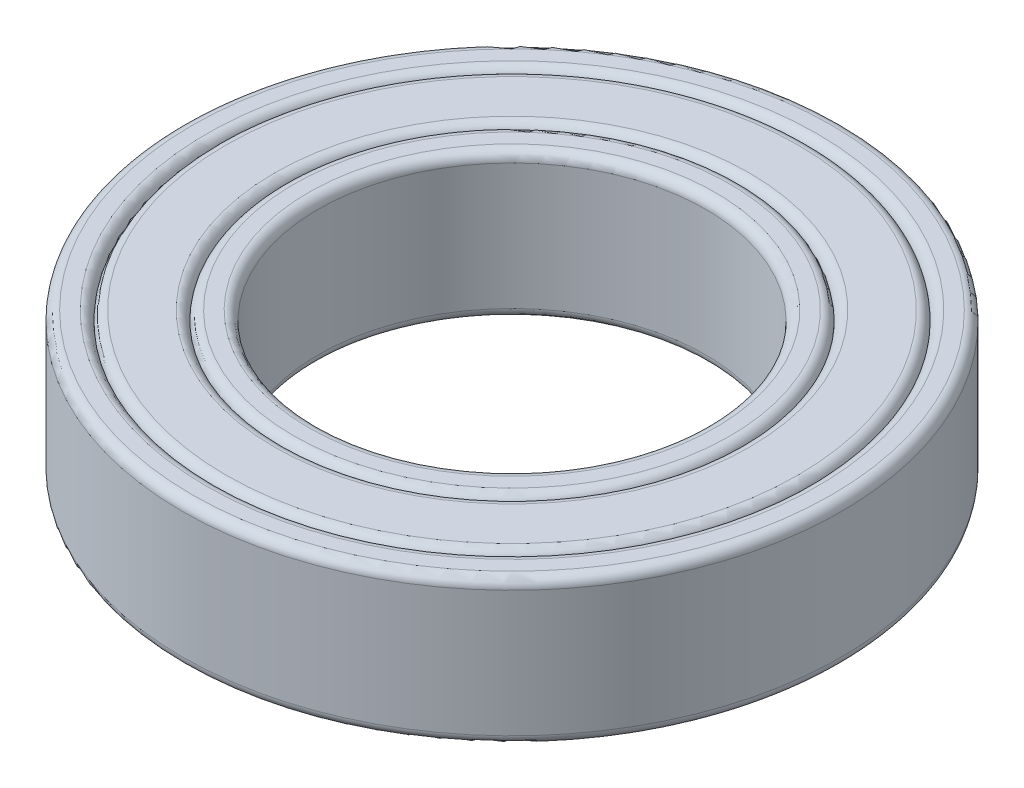
SolidWorks part; units mm, degrees
ref_plane "Front Plane" through (0, 0, 0) normal (0, 0, 1) x (1, 0, 0)
ref_plane "Top Plane" through (0, 0, 0) normal (0, 1, 0) x (1, 0, 0)
ref_plane "Right Plane" through (0, 0, 0) normal (1, 0, 0) x (0, 0, -1)
sketch "Sketch1" plane through (0, 0, 0) normal (0, 1, 0) x (1, 0, 0)
  circle A0 centre (0, 0) radius 34
  dimension "D1" = 68
extrude "Boss-Extrude1" add sketch "Sketch1" along normal mid plane 15
fillet "Fillet1" radius 1 2 edges at (0, -7.5, 34) (0, 7.5, 34)
sketch "Sketch2" plane through (0, 0, 0) normal (0, 1, 0) x (1, 0, 0)
  circle A0 centre (0, 0) radius 30.5
  dimension "D1" = 61
extrude "Cut-Extrude1" cut sketch "Sketch2" against normal through all both and the other way through all
fillet "Fillet2" radius 1 2 edges at (0, 7.5, 30.5) (0, -7.5, 30.5)
sketch "Sketch3" plane through (0, 0, 0) normal (0, 1, 0) x (1, 0, 0)
  circle A0 centre (0, 0) radius 30.5
  dimension "D1" = 61
extrude "Boss-Extrude2" add sketch "Sketch3" along normal through all and the other way through all
fillet "Fillet3" radius 1 2 edges at (0, -7.5, 30.5) (0, 7.5, 30.5)
sketch "Sketch4" plane through (0, 0, 0) normal (0, 1, 0) x (1, 0, 0)
  circle A0 centre (0, 0) radius 23.5
  dimension "D1" = 47
extrude "Cut-Extrude2" cut sketch "Sketch4" against normal through all both and the other way through all
fillet "Fillet4" radius 1 2 edges at (0, 7.5, 23.5) (0, -7.5, 23.5)
sketch "Sketch5" plane through (0, 0, 0) normal (0, 1, 0) x (1, 0, 0)
  circle A0 centre (0, 0) radius 23.5
  dimension "D1" = 47
extrude "Boss-Extrude3" add sketch "Sketch5" along normal through all and the other way through all
fillet "Fillet5" radius 1 2 edges at (0, -7.5, 23.5) (0, 7.5, 23.5)
sketch "Sketch6" plane through (0, 0, 0) normal (0, 1, 0) x (1, 0, 0)
  circle A0 centre (0, 0) radius 20
  dimension "D1" = 40
extrude "Cut-Extrude3" cut sketch "Sketch6" against normal through all both and the other way through all
fillet "Fillet6" radius 1 2 edges at (0, 7.5, 20) (0, -7.5, 20)
equation "\"D1@Boss-Extrude1\" = \"ARM Rotating Bearing Thickness\""
equation "\"D1@Sketch1\" = \"ARM Rotating Bearing OD\""
equation "\"D1@Fillet1\" = \"ALL Medium Fillet\""
equation "\"D1@Fillet2\" = \"ALL Medium Fillet\""
equation "\"D1@Fillet3\" = \"ALL Medium Fillet\""
equation "\"D1@Fillet4\" = \"ALL Medium Fillet\""
equation "\"D1@Fillet5\" = \"ALL Medium Fillet\""
equation "\"D1@Fillet6\"= \"ALL Medium Fillet\""
equation "\"D1@Sketch2\" = \"ARM Rotating Bearing OD\" - ( ( \"ARM Rotating Bearing OD\" - \"ARM Rotating Bearing ID\" ) / 4 )"
equation "\"D1@Sketch6\" = \"ARM Rotating Bearing ID\""
equation "\"D1@Sketch4\" = \"ARM Rotating Bearing ID\" + ( ( \"ARM Rotating Bearing OD\" - \"ARM Rotating Bearing ID\" ) / 4 )"
equation "\"D1@Sketch3\" = \"ARM Rotating Bearing OD\" - ( ( \"ARM Rotating Bearing OD\" - \"ARM Rotating Bearing ID\" ) / 4 )"
equation "\"D1@Sketch5\" = \"ARM Rotating Bearing ID\" + ( ( \"ARM Rotating Bearing OD\" - \"ARM Rotating Bearing ID\" ) / 4 )"
equation "\"ALL Big Fillet\"= 10.0mm"
equation "\"ALL Medium Fillet\"= 1.0mm"
equation "\"ALL Small Fillet\"= 0.5mm"
equation "\"BODY Rad\"= 82.5mm"
equation "\"BODY End Cut Rad\"= 72.5mm"
equation "\"BODY Height Ext\"= 27.5mm"
equation "\"BODY Bottom Cut Dist\"= 50.0mm"
equation "\"BODY Seal Thickness\"= 3.75mm"
equation "\"BODY Wall Extra Thickness\"= 2.5mm"
equation "\"BODY Bottom Extra Nut Wall\"= 7.5mm"
equation "\"ARM Both Dia\"= 39.75mm"
equation "\"ARM Both Length\"= 67.5mm"
equation "\"ARM Both Wire Hole Dia\"= 15.0mm"
equation "\"ARM Both Prop Seal Thickness\"= 2.5mm"
equation "\"ARM Both Brass Insert Dia\"= 4.875mm"
equation "\"ARM Both Bolt Cut Depth\"= 12.5mm"
equation "\"ARM Both Nema Bolt Off\"= 15.4mm"
equation "\"ARM Both Nema Bolt Depth\"= 2.5mm"
equation "\"ARM Both Nema Width\"= 20.0mm"
equation "\"ARM Both Nema Wall Off\"= 2.5mm"
equation "\"ARM Both Nema Center Dia 1\"= 17.0mm"
equation "\"ARM Both Nema Center Dia 2\"= 10.0mm"
equation "\"ARM Both Nema Bearing OD\"= 16.0mm"
equation "\"ARM Both Nema Bearing ID\"= 10.0mm"
equation "\"ARM Both Nema Bearing Thickness\"= 4.0mm"
equation "\"ARM Both Nema Height\"= 38.0mm"
equation "\"ARM Both Nema Shaft Dia\"= 4.0mm"
equation "\"ARM Both Nema Shaft Length\"= 10.0mm"
equation "\"ARM Both Nema Center Height\"= 1.5mm"
equation "\"ARM Rotating Bearing OD\"= 68.0mm"
equation "\"ARM Rotating Bearing ID\"= 40.0mm"
equation "\"ARM Rotating Bearing Thickness\"= 15.0mm"
equation "\"ARM Static Mount Dia\"= 65.0mm"
equation "\"ARM Static Bolt Off\"= 1.125mm"
equation "\"ALL Bolt Hole Off\"= 0.25mm"
equation "\"ALL Vert Bolt Hole Off Scalar\"= 0.5mm"
equation "\"ALL Horz Bolt Hole Off Scalar\"= 1.25mm"
equation "\"ALL Nut Size Off\"= 0.25mm"
equation "\"ALL Vert Nut Off Scalar\"= 0.5mm"
equation "\"ALL Horz Nut Off Scalar\"= 1.25mm"
equation "\"BODY Bolt Count\"= 12"
equation "\"BODY Bolt Size\"= 6"
equation "\"BODY Bolt Length\"= 22.0mm"
equation "\"BODY Bolt Head Dia\"= IIF ( \"BODY Bolt Size\" = 3 , 5.75mm , IIF ( \"BODY Bolt Size\" = 4 , 7.25mm , IIF ( \"BODY Bolt Size\" = 5 , 8.75mm , IIF ( \"BODY Bolt Size\" = 6 , 10.25mm , 5.75mm ) ) ) )"
equation "\"BODY Bolt Head Height\"= IIF ( \"BODY Bolt Size\" = 3 , 3.0mm , IIF ( \"BODY Bolt Size\" = 4 , 4.0mm , IIF ( \"BODY Bolt Size\" = 5 , 5.0mm , IIF ( \"BODY Bolt Size\" = 6 , 6.0mm , 3.0mm ) ) ) )"
equation "\"BODY Nut Width\"= IIF ( \"BODY Bolt Size\" = 3 , 5.5mm , IIF ( \"BODY Bolt Size\" = 4 , 7.0mm , IIF ( \"BODY Bolt Size\" = 5 , 8.0mm , IIF ( \"BODY Bolt Size\" = 6 , 10.0mm , 5.5mm ) ) ) )"
equation "\"BODY Nut Height\"= IIF ( \"BODY Bolt Size\" = 3 , 4.0mm , IIF ( \"BODY Bolt Size\" = 4 , 5.0mm , IIF ( \"BODY Bolt Size\" = 5 , 5.0mm , IIF ( \"BODY Bolt Size\" = 6 , 6.0mm , 4.0mm ) ) ) )"
equation "\"ARM Static Bolt Count\"= 8"
equation "\"ARM Static Bolt Size\"= 5"
equation "\"ARM Static Bolt Length\"= 20.0mm"
equation "\"ARM Static Bolt Head Dia\"= IIF ( \"ARM Static Bolt Size\" = 3 , 5.75mm , IIF ( \"ARM Static Bolt Size\" = 4 , 7.25mm , IIF ( \"ARM Static Bolt Size\" = 5 , 8.75mm , IIF ( \"ARM Static Bolt Size\" = 6 , 10.25mm , 5.75mm ) ) ) )"
equation "\"ARM Static Bolt Head Height\"= IIF ( \"ARM Static Bolt Size\" = 3 , 3.0mm , IIF ( \"ARM Static Bolt Size\" = 4 , 4.0mm , IIF ( \"ARM Static Bolt Size\" = 5 , 5.0mm , IIF ( \"ARM Static Bolt Size\" = 6 , 6.0mm , 3.0mm ) ) ) )"
equation "\"ARM Static Nut Width\"= IIF ( \"ARM Static Bolt Size\" = 3 , 5.5mm , IIF ( \"ARM Static Bolt Size\" = 4 , 7.0mm , IIF ( \"ARM Static Bolt Size\" = 5 , 8.0mm , IIF ( \"ARM Static Bolt Size\" = 6 , 10.0mm , 5.5mm ) ) ) )"
equation "\"ARM Static Nut Height\"= IIF ( \"ARM Static Bolt Size\" = 3 , 4.0mm , IIF ( \"ARM Static Bolt Size\" = 4 , 5.0mm , IIF ( \"ARM Static Bolt Size\" = 5 , 5.0mm , IIF ( \"ARM Static Bolt Size\" = 6 , 6.0mm , 4.0mm ) ) ) )"
equation "\"ARM Gear Width\"= 10.0mm"
equation "\"ARM Gear Width Off\"= 2.5mm"
equation "\"ARM Gear Bolt Count\"= 4"
equation "\"ARM Gear Rotation\"= 360.0deg"
equation "\"ARM Gear Bolt Size\"= 3"
equation "\"ARM Gear Bolt Length\"= 20.0mm"
equation "\"ARM Gear Bolt Head Dia\"= IIF ( \"ARM Static Bolt Size\" = 3 , 5.75mm , IIF ( \"ARM Static Bolt Size\" = 4 , 7.25mm , IIF ( \"ARM Static Bolt Size\" = 5 , 8.75mm , IIF ( \"ARM Static Bolt Size\" = 6 , 10.25mm , 5.75mm ) ) ) )"
equation "\"ARM Gear Bolt Head Height\"= IIF ( \"ARM Static Bolt Size\" = 3 , 3.0mm , IIF ( \"ARM Static Bolt Size\" = 4 , 4.0mm , IIF ( \"ARM Static Bolt Size\" = 5 , 5.0mm , IIF ( \"ARM Static Bolt Size\" = 6 , 6.0mm , 3.0mm ) ) ) )"
equation "\"ARM Gear Nut Width\"= IIF ( \"ARM Static Bolt Size\" = 3 , 5.5mm , IIF ( \"ARM Static Bolt Size\" = 4 , 7.0mm , IIF ( \"ARM Static Bolt Size\" = 5 , 8.0mm , IIF ( \"ARM Static Bolt Size\" = 6 , 10.0mm , 5.5mm ) ) ) )"
equation "\"ARM Gear Nut Height\"= IIF ( \"ARM Static Bolt Size\" = 3 , 4.0mm , IIF ( \"ARM Static Bolt Size\" = 4 , 5.0mm , IIF ( \"ARM Static Bolt Size\" = 5 , 5.0mm , IIF ( \"ARM Static Bolt Size\" = 6 , 6.0mm , 4.0mm ) ) ) )"
equation "\"ARM Both Prop Plate Bolt Size\"= 3"
equation "\"ARM Both Prop Plate Bolt Length\"= 16.0mm"
equation "\"ARM Both Prop Plate Bolt Head Dia\"= IIF ( \"ARM Both Prop Plate Bolt Size\" = 3 , 5.75mm , IIF ( \"ARM Both Prop Plate Bolt Size\" = 4 , 7.25mm , IIF ( \"ARM Both Prop Plate Bolt Size\" = 5 , 8.75mm , IIF ( \"ARM Both Prop Plate Bolt Size\" = 6 , 10.25mm , 5.75mm ) ) ) )"
equation "\"ARM Both Prop Plate Bolt Head Height\"= IIF ( \"ARM Both Prop Plate Bolt Size\" = 3 , 3.0mm , IIF ( \"ARM Both Prop Plate Bolt Size\" = 4 , 4.0mm , IIF ( \"ARM Both Prop Plate Bolt Size\" = 5 , 5.0mm , IIF ( \"ARM Both Prop Plate Bolt Size\" = 6 , 6.0mm , 3.0mm ) ) ) )"
equation "\"ARM Both Nema Bolt Size\"= 2"
equation "\"ARM Both Nema Bolt Head Dia\"= IIF ( \"ARM Both Nema Bolt Size\" = 3 , 5.75mm , IIF ( \"ARM Both Nema Bolt Size\" = 4 , 7.25mm , IIF ( \"ARM Both Nema Bolt Size\" = 5 , 8.75mm , IIF ( \"ARM Both Nema Bolt Size\" = 6 , 10.25mm , 5.75mm ) ) ) )"
equation "\"ARM Both Nema Bolt Head Height\"= IIF ( \"ARM Both Nema Bolt Size\" = 3 , 3.0mm , IIF ( \"ARM Both Nema Bolt Size\" = 4 , 4.0mm , IIF ( \"ARM Both Nema Bolt Size\" = 5 , 5.0mm , IIF ( \"ARM Both Nema Bolt Size\" = 6 , 6.0mm , 3.0mm ) ) ) )"
